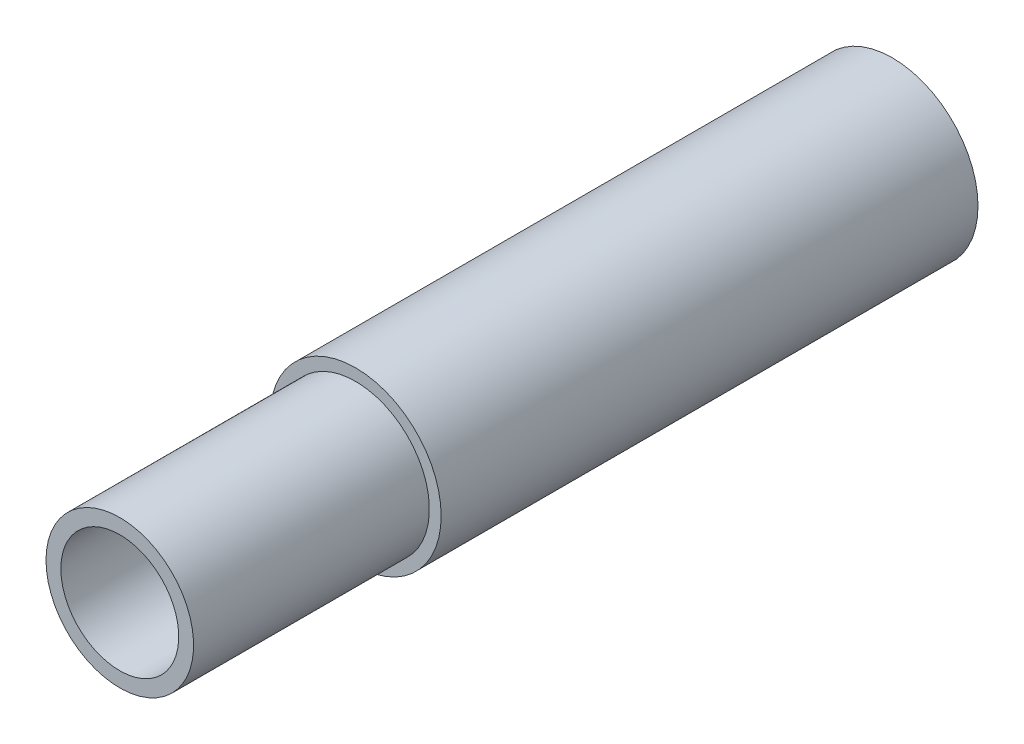
SolidWorks part; units mm, degrees
material "Silicon Rubber"
ref_plane "X-Y Datum" through (0, 0, 0) normal (0, 0, 1) x (1, 0, 0)
ref_plane "X-Z Datum" through (0, 0, 0) normal (0, 1, 0) x (1, 0, 0)
ref_plane "Y-Z Datum" through (0, 0, 0) normal (1, 0, 0) x (0, 0, -1)
sketch "Master Sketch" plane through (0, 0, 0) normal (0, 1, 0) x (1, 0, 0)
  line L0 (0, 0) -> (0, 50.8)
  line L2 (-9.525, 84.9884) -> (9.525, 84.9884) construction
  line L3 (-9.525, 95.5675) -> (9.525, 95.5675) construction
  line L4 (-9.525, 84.9884) -> (9.525, 84.9884) construction
  line L5 (-9.525, 95.5675) -> (9.525, 95.5675) construction
  line L6 (0, 84.9884) -> (0, 95.5675) construction
  line L7 (0, 50.8) -> (0, 104.0384)
  dimension "D1" = 19.05
  dimension "D4" = 50.8
sketch "Sketch9" plane through (0, 0, 0) normal (0, 1, 0) x (1, 0, 0)
  line L1 (0, 0) -> (0, 31.75)
  dimension "D1" = 31.75
sweep "Sweep1" add path "Sketch9" circular profile diameter 19.875 parameters "D3"=19.875
sweep "Cut-Sweep1" cut path "Sketch9<2>" circular profile diameter 15.875 parameters "D3"=15.875
sketch "Sketch9<2>" plane through (0, 0, 0) normal (0, 1, 0) x (1, 0, 0) same geometry as "Sketch9"
sketch "Sketch31" plane through (0, 0, 0) normal (0, 1, 0) x (1, 0, 0)
  line L0 (-9.525, 84.9884) -> (9.525, 84.9884) construction
  line L1 (-9.6754, 91.7558) -> (9.6754, 91.7558) construction
  line L2 (-9.525, 84.9884) -> (9.525, 84.9884) construction
  line L3 (-9.6754, 91.7558) -> (9.6754, 91.7558) construction
  line L4 (0, 91.7558) -> (0, 84.9884) construction
  line L5 (7.9375, 31.75) -> (-7.9375, 31.75) construction
  line L6 (7.9375, 31.75) -> (-7.9375, 31.75) construction
  line L7 (0, 31.75) -> (0, 104.0384)
  dimension "D1" = 19.05
sweep "Sweep2" add path "Sketch31" circular profile diameter 23.05 parameters "D3"=23.05
sweep "Cut-Sweep2" cut path "Sketch31<2>" circular profile diameter 19.05 parameters "D3"=19.05
sketch "Sketch31<2>" plane through (0, 0, 0) normal (0, 1, 0) x (1, 0, 0) same geometry as "Sketch31"
